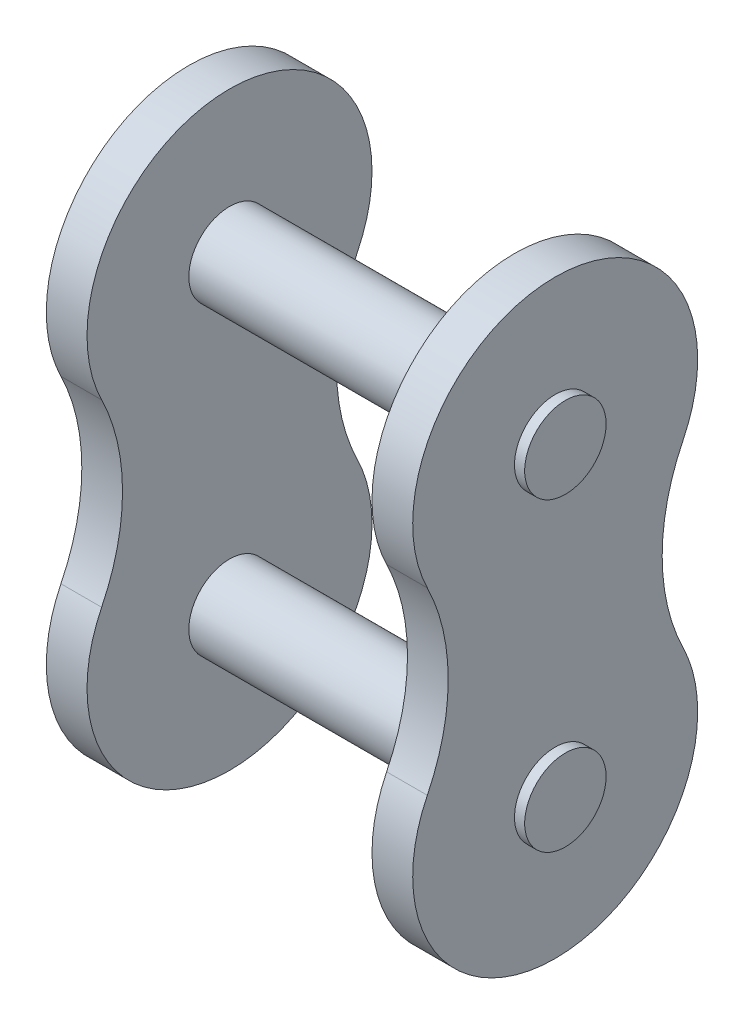
SolidWorks part; units mm, degrees
material "AISI 1045 Steel, cold drawn"
ref_plane "Front Plane" through (0, 0, 0) normal (1, 0, 0) x (0, 1, 0)
ref_plane "Top Plane" through (0, 0, 0) normal (0, 0, 1) x (0, 1, 0)
ref_plane "Right Plane" through (0, 0, 0) normal (0, 1, 0) x (-1, 0, 0)
sketch "Sketch2" plane through (0, 0, 0) normal (1, 0, 0) x (0, 1, 0)
  line L0 (0, 6.1479) -> (0, -6.8413) construction
  line L1 (-7.25, 0) -> (7.25, 0) construction
  circle A0 centre (-3.75, 0) radius 1
  circle A1 centre (3.75, 0) radius 1
  circle A2 centre (-3.75, 0) radius 3.5
  circle A3 centre (3.75, 0) radius 3.5
  arc A4 (-2.2059, 3.141) -> (2.2059, 3.141) centre (0, 7.6281) ccw
  arc A5 (-2.2059, -3.141) -> (2.2059, -3.141) centre (0, -7.6281) cw
  circle A6 centre (-3.75, 0) radius 1.5
  circle A7 centre (3.75, 0) radius 1.5
  dimension "D1" = 2
  dimension "D3" = 7
  dimension "D4" = 5
  dimension "D5" = 3
  dimension "D2" = 7.5
extrude "Boss-Extrude1" add sketch "Sketch2" against normal blind 1 contours A3 A7 | A2 A5 A3 A4 | A7 A1 | A0 | A2 region at (0, 0, 0) region at (0, 5.5478, 2.887) region at (0, 2.2924, 0)
extrude "Boss-Extrude2" add sketch "Sketch2<3>" along normal blind 3.5 and the other way blind 1.25 contours A0 | A1 region at (0, -3.75, 0) region at (0, 3.75, 0)
sketch "Sketch2<3>" plane through (0, 0, 0) normal (1, 0, 0) x (0, 1, 0) same geometry as "Sketch2"
move or copy body "Body-Move/Copy3" [suppressed] bodies to move or copy 102 copy yes number of copies 1 rotation origin (0.75, 0, 0) rotation axis (0, 1, 0) rotation angle 180
ref_plane "Plane1" through (3.5, 0, 0) normal (1, 0, 0) x (0, 1, 0)
mirror "Mirror1" about plane through (3.5, 0, 0) normal (1, 0, 0) of bodies 102
